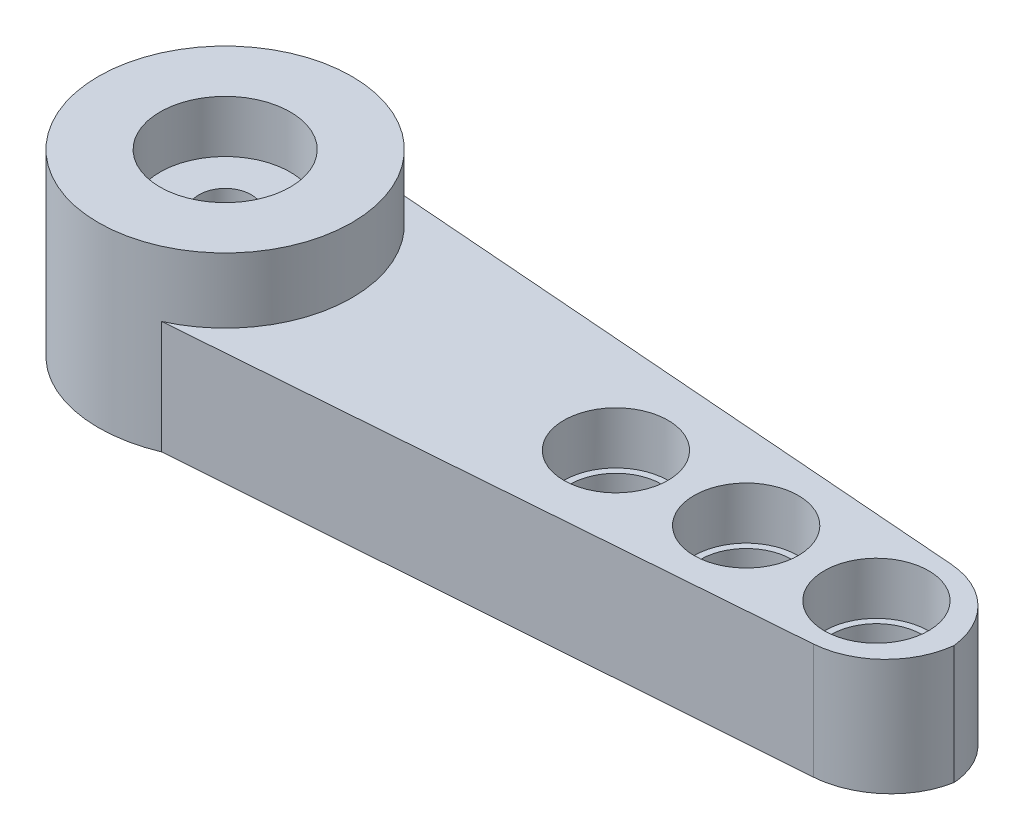
SolidWorks part; units mm, degrees
other "Camera1"
material "ABS"
ref_plane "Front Plane" through (0, 0, 0) normal (0, 0, 1) x (1, 0, 0)
ref_plane "Top Plane" through (0, 0, 0) normal (0, 1, 0) x (1, 0, 0)
ref_plane "Right Plane" through (0, 0, 0) normal (1, 0, 0) x (0, 0, -1)
sketch "Sketch1" plane through (0, 0, 0) normal (0, 1, 0) x (1, 0, 0)
  line L0 (-17.2, 0) -> (17.2, 0) construction
  line L1 (0, -8.35) -> (0, 8.35) construction
  line L2 (-15.2, 2) -> (-2, 2.95)
  line L3 (-15.2, -2) -> (-2, -2.95)
  line L4 (2, 6.35) -> (2, 3.5)
  line L5 (-2, 6.35) -> (-2, 2.95)
  line L6 (2, -6.35) -> (2, -3.5)
  line L7 (-2, -6.35) -> (-2, -2.95)
  line L8 (15.2, 2) -> (2, 3.5)
  line L9 (15.2, -2) -> (2, -3.5)
  circle A0 centre (0, 0) radius 3.5 construction
  arc A1 (-15.2, 2) -> (-15.2, -2) centre (-15.2, 0) ccw
  arc A2 (15.2, 2) -> (15.2, -2) centre (15.2, 0) cw
  arc A3 (2, 6.35) -> (-2, 6.35) centre (0, 6.35) ccw
  circle A4 centre (0, 6.35) radius 0.6
  circle A5 centre (0, 4.75) radius 0.6
  circle A6 centre (0, -4.75) radius 0.6
  circle A7 centre (0, -6.35) radius 0.6
  arc A8 (2, -6.35) -> (-2, -6.35) centre (0, -6.35) cw
  circle A10 centre (-15.2, 0) radius 0.6
  circle A11 centre (15.2, 0) radius 0.6
  circle A12 centre (-13.4, 0) radius 0.6
  circle A13 centre (-11.6, 0) radius 0.6
  circle A14 centre (-9.8, 0) radius 0.6
  circle A15 centre (-8, 0) radius 0.6
  circle A16 centre (-6.2, 0) radius 0.6
  circle A17 centre (-4.4, 0) radius 0.6
  circle A18 centre (13.4, 0) radius 0.6
  circle A19 centre (11.6, 0) radius 0.6
  circle A20 centre (9.8, 0) radius 0.6
  circle A21 centre (8, 0) radius 0.6
  circle A22 centre (6.2, 0) radius 0.6
  circle A23 centre (4.4, 0) radius 0.6
  point P5 (0, 0)
  point P8 (0, 0)
  point P25 (0, 6.95)
  point P26 (0, 4.15)
  dimension "D1" = 7
  dimension "D4" = 4
  dimension "D6" = 1.2
  dimension "D2" = 34.4
  dimension "D3" = 16.7
  dimension "D5" = 2
  dimension "D7" = 2.8
  dimension "D8" = 7
  dimension "D10" = 5.9
  dimension "D11" = 7
  dimension "D12" = 7
extrude "Boss-Extrude1" add sketch "Sketch1" along normal blind 1.4
sketch "Sketch2" plane through (0, 0, 0) normal (0, -1, 0) x (1, 0, 0)
  circle A0 centre (0, 0) radius 2.6
  dimension "D1" = 5.2
extrude "Cut-Extrude1" cut sketch "Sketch2" against normal blind 1
sketch "Sketch3" plane through (0, 1.4, 0) normal (0, 1, 0) x (1, 0, 0)
  circle A0 centre (0, 0) radius 1
  circle A1 centre (0, 0) radius 3.5
  dimension "D1" = 2
  dimension "D2" = 7
extrude "Boss-Extrude2" add sketch "Sketch3" along normal blind 2.5
sketch "Sketch4" plane through (0, 1.4, 0) normal (0, 1, 0) x (1, 0, 0)
  circle A0 centre (0, 0) radius 1.2
  dimension "D1" = 2.4
extrude "Cut-Extrude2" cut sketch "Sketch4" against normal through all
sketch "Sketch6" plane through (0, 0, 0) normal (0, -1, 0) x (1, 0, 0)
  line L0 (-2, -2.95) -> (-15.2, -2) construction
  line L1 (-1.8686, -2.9595) -> (-15.2, -2)
  line L2 (-15.2, 2) -> (-2, 2.95) construction
  line L3 (-15.2, 2) -> (-1.8686, 2.9595)
  line L4 (0, -9.3016) -> (0, 8.6978) construction
  line L5 (1.8686, -2.9595) -> (15.2, -2)
  line L6 (15.2, 2) -> (1.8686, 2.9595)
  line L8 (-17.8676, -8.836) -> (17.8676, -8.836)
  line L9 (-17.8676, -8.836) -> (-17.8676, 8.836)
  line L10 (-17.8676, 8.836) -> (17.8676, 8.836)
  line L11 (17.8676, -8.836) -> (17.8676, 8.836)
  line L12 (-17.8676, -8.836) -> (17.8676, 8.836) construction
  line L13 (-17.8676, 8.836) -> (17.8676, -8.836) construction
  arc A0 (-15.2, 2) -> (-15.2, -2) centre (-15.2, 0) ccw construction
  arc A1 (-15.2, 2) -> (-15.2, -2) centre (-15.2, 0) ccw
  circle A2 centre (0, 0) radius 3.5 construction
  arc A3 (1.8686, 2.9595) -> (-1.8686, 2.9595) centre (0, 0) ccw
  arc A4 (15.2, 2) -> (15.2, -2) centre (15.2, 0) cw
  arc A5 (-1.8686, -2.9595) -> (1.8686, -2.9595) centre (0, 0) ccw
extrude "Cut-Extrude4" cut sketch "Sketch6" against normal through all
sketch "Sketch7" plane through (0, 0, 0) normal (0, -1, 0) x (1, 0, 0)
  line L0 (0, 3.5) -> (-17.7318, 3.5)
  line L1 (-17.7318, 3.5) -> (-17.7318, -3.5)
  line L2 (-17.7318, -3.5) -> (0, -3.5)
  circle A0 centre (0, 0) radius 3.5 construction
  arc A1 (0, 3.5) -> (0, -3.5) centre (0, 0) ccw
extrude "Cut-Extrude5" cut sketch "Sketch7" against normal through all
sketch "草圖1" plane through (0, 1.4, 0) normal (0, 1, 0) x (1, 0, 0)
  line L1 (15.2, 2) -> (23.2, 2)
  line L2 (15.2, 2) -> (15.2, -2)
  line L3 (15.2, -2) -> (23.2, -2)
  circle A0 centre (17.2, 0) radius 0.75
  arc A1 (15.2, -2) -> (15.2, 2) centre (15.2, 0) ccw construction
  circle A2 centre (19.2, 0) radius 0.75
  circle A3 centre (21.2, 0) radius 0.75
  circle A4 centre (23.2, 0) radius 0.75
  arc A5 (23.2, 2) -> (23.2, -2) centre (23.2, 0) cw
  dimension "D1" = 8
  dimension "D5" = 2
  dimension "D6" = 1.5
  dimension "D2" = 2
  dimension "D3" = 2
  dimension "D4" = 2
extrude "填料-伸長1" add sketch "草圖1" against normal blind 2
sketch "草圖2" plane through (0, 0, 0) normal (0, -1, 0) x (1, 0, 0)
  line L4 (1.8686, -2.9595) -> (15.2, -2)
  line L5 (1.8686, -2.9595) -> (15.2, -2)
  line L6 (15.2, -2) -> (15.2, -0.6)
  line L7 (15.2, -2) -> (15.2, -0.6)
  line L12 (15.2, 0.6) -> (15.2, 2)
  line L13 (15.2, 0.6) -> (15.2, 2)
  line L14 (15.2, 2) -> (1.8686, 2.9595)
  line L15 (15.2, 2) -> (1.8686, 2.9595)
  circle A0 centre (8, 0) radius 0.6 construction
  circle A1 centre (8, 0) radius 0.6
  arc A2 (15.2, 0.6) -> (15.2, -0.6) centre (15.2, 0) ccw
  circle A6 centre (4.4, 0) radius 0.6 construction
  circle A7 centre (6.2, 0) radius 0.6 construction
  circle A8 centre (9.8, 0) radius 0.6 construction
  circle A9 centre (11.6, 0) radius 0.6 construction
  circle A10 centre (13.4, 0) radius 0.6 construction
  circle A13 centre (13.4, 0) radius 0.6
  circle A14 centre (11.6, 0) radius 0.6
  circle A15 centre (9.8, 0) radius 0.6
  circle A16 centre (6.2, 0) radius 0.6
  circle A17 centre (4.4, 0) radius 0.6
  circle A18 centre (0, 0) radius 1.2 construction
  circle A19 centre (0, 0) radius 2.6 construction
  circle A20 centre (0, 0) radius 1.2
  circle A21 centre (0, 0) radius 2.6
  arc A22 (15.2, 0.6) -> (15.2, -0.6) centre (15.2, 0) ccw
  arc A24 (1.8686, 2.9595) -> (1.8686, -2.9595) centre (0, 0) ccw
  arc A25 (1.8686, 2.9595) -> (1.8686, -2.9595) centre (0, 0) ccw
  circle M10 centre (0, 0) radius 2.6
  line M11 (1.8686, -2.9595) -> (15.2, -2)
  line M12 (15.2, -2) -> (15.2, -0.6)
  arc M13 (15.2, -0.6) -> (15.2, 0.6) centre (15.2, 0) cw
  line M14 (15.2, 0.6) -> (15.2, 2)
  line M15 (15.2, 2) -> (1.8686, 2.9595)
  arc M16 (1.8686, 2.9595) -> (1.8686, -2.9595) centre (0, 0) ccw
  circle M17 centre (13.4, 0) radius 0.6
  circle M18 centre (11.6, 0) radius 0.6
  circle M19 centre (9.8, 0) radius 0.6
  circle M20 centre (8, 0) radius 0.6
  circle M21 centre (6.2, 0) radius 0.6
  circle M22 centre (4.4, 0) radius 0.6
  dimension "D1" = 0
extrude "填料-伸長2" add sketch "草圖2" along normal blind 0.6 contours M16 M11 M12 M13 M14 M15 M18 M20 M22 M21 M19 M17 M10 region at (-3.3003, 0, 0)
sketch "草圖3" plane through (0, -0.6, 0) normal (0, -1, 0) x (1, 0, 0)
  line L0 (15.2, -0.6) -> (15.2, 0.6) construction
  circle A0 centre (17.2, 0) radius 0.75
  arc A1 (17.0594, -0.7367) -> (17.0594, 0.7367) centre (15.2, 0) ccw construction
  circle A2 centre (15.2, 0) radius 0.6
extrude "除料-伸長1" cut sketch "草圖3" against normal through all and the other way through all
sketch "草圖4" plane through (0, -0.6, 0) normal (0, -1, 0) x (1, 0, 0)
  line L0 (1.8686, -2.9595) -> (15.2, -2) construction
  line L1 (15.2, 2) -> (1.8686, 2.9595) construction
  line L2 (1.8686, 2.9595) -> (3.9728, 2.808)
  line L3 (1.8686, -2.9595) -> (3.9728, -2.808)
  arc A0 (1.8686, 2.9595) -> (1.8686, -2.9595) centre (0, 0) ccw
  arc A1 (3.9728, 2.808) -> (3.9728, -2.808) centre (0, 0) ccw
extrude "填料-伸長3" add sketch "草圖4" against normal up to surface (4.5 mm away) up to face at (0, 3.9, 3.5)
sketch "草圖5" plane through (0, -0.6, 0) normal (0, -1, 0) x (1, 0, 0)
  line L0 (2, 4.4349) -> (28, 2.4349)
  line L5 (28, 2.4349) -> (28, -2.4349)
  line L6 (28, -2.4349) -> (2, -4.4349)
  line L7 (2, 4.4349) -> (3, 0)
  line L8 (3, 0) -> (2, -4.4349)
  arc A0 (3.9728, 2.808) -> (3.9728, -2.808) centre (0, 0) ccw construction
  dimension "D1" = 2
  dimension "D2" = 2
  dimension "D3" = 25
  dimension "D4" = 3
  dimension "D5" = 2
extrude "填料-伸長4" add sketch "草圖5" against normal up to surface (2 mm away) up to face at (17.2, 1.4, 0.75)
sketch "草圖7" plane through (0, -0.6, 0) normal (0, -1, 0) x (1, 0, 0)
  line L0 (28, -2.4349) -> (28, 2.4349) construction
  circle A0 centre (20, 0) radius 2
  circle A1 centre (25, 0) radius 2
  circle A2 centre (15, 0) radius 2
  dimension "D1" = 4
  dimension "D2" = 8
  dimension "D3" = 5
  dimension "D4" = 5
extrude "除料-伸長2" cut sketch "草圖7" against normal up to surface (2 mm away) and the other way blind 10 contours A2 | A1 | A0 region at (25, -0.6, 0) region at (15, -0.6, 0) up to face at (9.1915, 1.4, 0)
fillet "圓角1" radius 3 2 edges at (28, 0.4, -2.4349) (28, 0.4, 2.4349)
sketch "草圖9" plane through (0, -0.6, 0) normal (0, -1, 0) x (1, 0, 0)
  line L2 (2, -4.4349) -> (25.2301, -2.648)
  line L3 (25.2301, 2.648) -> (2, 4.4349)
  line L4 (2, -4.4349) -> (25.2301, -2.648)
  line L5 (25.2301, 2.648) -> (2, 4.4349)
  circle A0 centre (20, 0) radius 1.75
  circle A1 centre (0, 0) radius 2.6
  circle A2 centre (15, 0) radius 1.75
  arc A3 (25.2301, -2.648) -> (27.9803, 0) centre (25, 0.3432) ccw
  arc A4 (27.9803, 0) -> (25.2301, 2.648) centre (25, -0.3432) ccw
  arc A5 (2, 4.4349) -> (2, -4.4349) centre (0, 0) ccw
  arc A6 (25.2301, -2.648) -> (27.9803, 0) centre (25, 0.3432) ccw
  arc A7 (27.9803, 0) -> (25.2301, 2.648) centre (25, -0.3432) ccw
  arc A8 (2, 4.4349) -> (2, -4.4349) centre (0, 0) ccw
  circle A9 centre (25, 0) radius 1.75
  dimension "D2" = 3.5
  dimension "D1" = 0
extrude "填料-伸長5" add sketch "草圖9" along normal blind 3
sketch "草圖10" plane through (0, 3.9, 0) normal (0, 1, 0) x (1, 0, 0)
  circle A0 centre (0, 0) radius 4.865
  circle A1 centre (0, 0) radius 3.6257
extrude "填料-伸長6" add sketch "草圖10" against normal blind 5
ref_plane "平面4" through (0, -4, 0) normal (0, 1, 0) x (1, 0, 0)
ref_plane "平面5" through (0, 0, -5) normal (0, 0, 1) x (1, 0, 0)
ref_axis "基準軸2" through (29.6226, -4, -5) along (-1, 0, 0)
ref_plane "平面6" through (0, -3.7465, 0.1832) normal (0, 0.9988, -0.0488) x (-1, 0, 0)
sketch "草圖13" plane through (0, -3.7465, 0.1832) normal (0, 0.9988, -0.0488) x (-1, 0, 0)
  line L1 (6.4177, 13.3009) -> (-33.3725, 13.3009)
  line L2 (6.4177, 13.3009) -> (6.4177, -13.6842)
  line L3 (6.4177, -13.6842) -> (-33.3725, -13.6842)
  line L4 (-33.3725, 13.3009) -> (-33.3725, -13.6842)
extrude "除料-伸長5" cut sketch "草圖13" along normal blind 0.6 and the other way through all
sketch "草圖14" plane through (0, 3.9, 0) normal (0, 1, 0) x (1, 0, 0)
  circle A0 centre (0, 0) radius 4.865
  circle A1 centre (0, 0) radius 1
extrude "填料-伸長7" add sketch "草圖14" against normal up to surface (2.9 mm away) up to face at (0, 1, -1.2)
sketch "草圖15" plane through (0, 3.9, 0) normal (0, 1, 0) x (1, 0, 0)
  circle A0 centre (0, 0) radius 2.5
  dimension "D1" = 5
extrude "除料-伸長6" cut sketch "草圖15" against normal blind 2
sketch "草圖16" plane through (0, 1, 0) normal (0, -1, 0) x (1, 0, 0)
  circle A0 centre (0, 0) radius 2.6
  circle A1 centre (0, 0) radius 1
extrude "填料-伸長8" add sketch "草圖16" along normal blind 2
